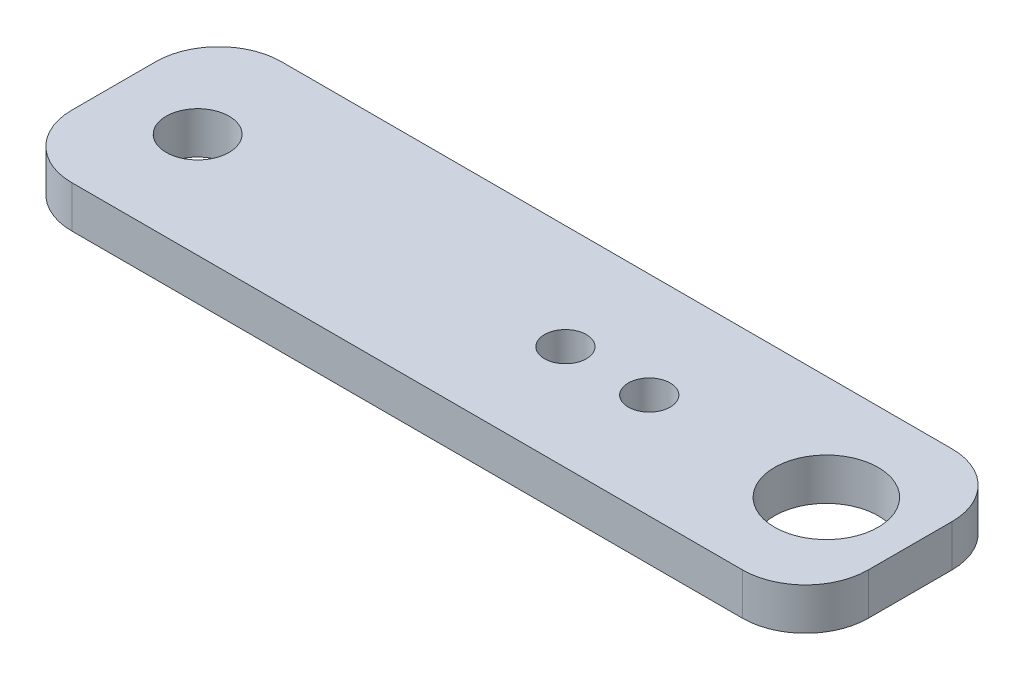
SolidWorks part; units mm, degrees
ref_plane "Front Plane" through (0, 0, 0) normal (0, 0, 1) x (1, 0, 0)
ref_plane "Top Plane" through (0, 0, 0) normal (0, 1, 0) x (1, 0, 0)
ref_plane "Right Plane" through (0, 0, 0) normal (1, 0, 0) x (0, 0, -1)
sketch "Sketch1" plane through (0, 0, 0) normal (0, 1, 0) x (1, 0, 0)
  line L1 (-19, 5) -> (19, 5)
  line L2 (-19, 5) -> (-19, -5)
  line L3 (-19, -5) -> (19, -5)
  line L4 (19, 5) -> (19, -5)
  line L5 (-19, 5) -> (19, -5) construction
  line L6 (-19, -5) -> (19, 5) construction
  point P0 (0, 0)
  dimension "D1" = 10
  dimension "D2" = 38
extrude "Boss-Extrude1" add sketch "Sketch1" along normal blind 2
sketch "Sketch2" plane through (0, 2, 0) normal (0, 1, 0) x (1, 0, 0)
  line L0 (15, 5) -> (15, -5) construction
  line L1 (-19, -5) -> (19, -5) construction
  line L2 (19, -5) -> (19, 5) construction
  circle A0 centre (15, 0) radius 2.4729
  circle A3 centre (6.55, 0) radius 1
  circle A4 centre (2.55, 0) radius 1
  point P10 (15, 0)
  dimension "D1" = 8.45
  dimension "D4" = 2
  dimension "D2" = 4
  dimension "D3" = 4
extrude "Cut-Extrude1" cut sketch "Sketch2" against normal blind 3
fillet "Fillet1" radius 3 4 edges at (19, 1, 5) (19, 1, -5) (-19, 1, -5) (-19, 1, 5)
hole_wizard "Ø3.0 (3) Diameter Hole1" positions "Sketch3" profile "Sketch4" hole size "Ø3.0" standard "BSI" end condition through all
sketch "Sketch3" plane through (0, 2, 0) normal (0, 1, 0) x (1, 0, 0)
  circle A1 centre (15, 0) radius 2.4729 construction
  point P0 (-15, 0)
  dimension "D1" = 30
sketch "Sketch4" plane through (-15, 2, 0) normal (1, 0, 0) x (0, 0, 1)
  line L0 (0, 0) -> (0, 2)
  line L1 (0, 2) -> (1.5, 2)
  line L2 (1.5, 2) -> (1.5, 0)
  line L5 (1.5, 0) -> (0, 0)
  line L11 (0, -6.35) -> (0, 107.95) construction
  dimension "Thru Hole Dia." = 3
  dimension "Thru Hole Depth" = 2
